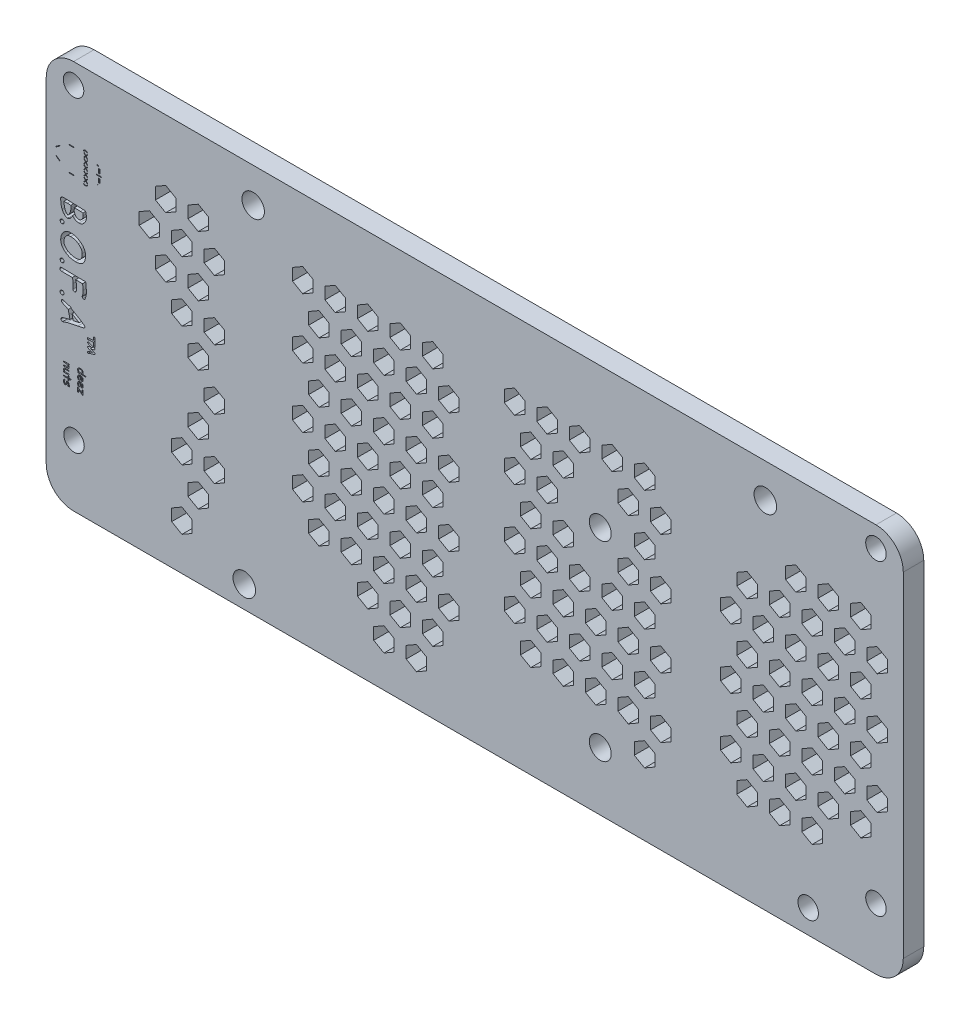
SolidWorks part; units mm, degrees
material "Acrylic (Medium-high impact)"
ref_plane "Front Plane" through (0, 0, 0) normal (0, 0, 1) x (1, 0, 0)
ref_plane "Top Plane" through (0, 0, 0) normal (0, 1, 0) x (1, 0, 0)
ref_plane "Right Plane" through (0, 0, 0) normal (1, 0, 0) x (0, 0, -1)
sketch "Sketch1" plane through (0, 0, 0) normal (0, 0, 1) x (1, 0, 0)
  line L1 (-44.0683, 22.5068) -> (73.4317, 22.5068)
  line L2 (-48.0683, 18.5068) -> (-48.0683, -30.4932)
  line L3 (-44.0683, -34.4932) -> (73.4317, -34.4932)
  line L4 (77.4317, 18.5068) -> (77.4317, -30.4932)
  line L41 (-32.9586, 9.1449) -> (-34.4586, 8.2789)
  line L42 (-34.4586, 8.2789) -> (-34.4586, 6.5468)
  line L43 (-34.4586, 6.5468) -> (-32.9586, 5.6808)
  line L44 (-32.9586, 5.6808) -> (-31.4586, 6.5468)
  line L45 (-31.4586, 6.5468) -> (-31.4586, 8.2789)
  line L46 (-31.4586, 8.2789) -> (-32.9586, 9.1449)
  line L47 (-30.5742, 13.5468) -> (-32.0742, 12.6808)
  line L48 (-32.0742, 12.6808) -> (-32.0742, 10.9488)
  line L49 (-32.0742, 10.9488) -> (-30.5742, 10.0827)
  line L50 (-30.5742, 10.0827) -> (-29.0742, 10.9488)
  line L51 (-29.0742, 10.9488) -> (-29.0742, 12.6808)
  line L52 (-29.0742, 12.6808) -> (-30.5742, 13.5468)
  line L53 (-28.1986, 9.1449) -> (-29.6986, 8.2789)
  line L54 (-29.6986, 8.2789) -> (-29.6986, 6.5468)
  line L55 (-29.6986, 6.5468) -> (-28.1986, 5.6808)
  line L56 (-28.1986, 5.6808) -> (-26.6986, 6.5468)
  line L57 (-26.6986, 6.5468) -> (-26.6986, 8.2789)
  line L58 (-26.6986, 8.2789) -> (-28.1986, 9.1449)
  line L59 (-25.8142, 13.5468) -> (-27.3142, 12.6808)
  line L60 (-27.3142, 12.6808) -> (-27.3142, 10.9488)
  line L61 (-27.3142, 10.9488) -> (-25.8142, 10.0827)
  line L62 (-25.8142, 10.0827) -> (-24.3142, 10.9488)
  line L63 (-24.3142, 10.9488) -> (-24.3142, 12.6808)
  line L64 (-24.3142, 12.6808) -> (-25.8142, 13.5468)
  line L65 (-23.4386, 9.1449) -> (-24.9386, 8.2789)
  line L66 (-24.9386, 8.2789) -> (-24.9386, 6.5468)
  line L67 (-24.9386, 6.5468) -> (-23.4386, 5.6808)
  line L68 (-23.4386, 5.6808) -> (-21.9386, 6.5468)
  line L69 (-21.9386, 6.5468) -> (-21.9386, 8.2789)
  line L70 (-21.9386, 8.2789) -> (-23.4386, 9.1449)
  line L95 (-30.5742, 4.7468) -> (-32.0742, 3.8808)
  line L96 (-32.0742, 3.8808) -> (-32.0742, 2.1488)
  line L97 (-32.0742, 2.1488) -> (-30.5742, 1.2827)
  line L98 (-30.5742, 1.2827) -> (-29.0742, 2.1488)
  line L99 (-29.0742, 2.1488) -> (-29.0742, 3.8808)
  line L100 (-29.0742, 3.8808) -> (-30.5742, 4.7468)
  line L101 (-28.1986, 0.3449) -> (-29.6986, -0.5211)
  line L102 (-29.6986, -0.5211) -> (-29.6986, -2.2532)
  line L103 (-29.6986, -2.2532) -> (-28.1986, -3.1192)
  line L104 (-28.1986, -3.1192) -> (-26.6986, -2.2532)
  line L105 (-26.6986, -2.2532) -> (-26.6986, -0.5211)
  line L106 (-26.6986, -0.5211) -> (-28.1986, 0.3449)
  line L107 (-25.8142, 4.7468) -> (-27.3142, 3.8808)
  line L108 (-27.3142, 3.8808) -> (-27.3142, 2.1488)
  line L109 (-27.3142, 2.1488) -> (-25.8142, 1.2827)
  line L110 (-25.8142, 1.2827) -> (-24.3142, 2.1488)
  line L111 (-24.3142, 2.1488) -> (-24.3142, 3.8808)
  line L112 (-24.3142, 3.8808) -> (-25.8142, 4.7468)
  line L113 (-23.4386, 0.3449) -> (-24.9386, -0.5211)
  line L114 (-24.9386, -0.5211) -> (-24.9386, -2.2532)
  line L115 (-24.9386, -2.2532) -> (-23.4386, -3.1192)
  line L116 (-23.4386, -3.1192) -> (-21.9386, -2.2532)
  line L117 (-21.9386, -2.2532) -> (-21.9386, -0.5211)
  line L118 (-21.9386, -0.5211) -> (-23.4386, 0.3449)
  line L155 (-25.8142, -4.0532) -> (-27.3142, -4.9192)
  line L156 (-27.3142, -4.9192) -> (-27.3142, -6.6512)
  line L157 (-27.3142, -6.6512) -> (-25.8142, -7.5173)
  line L158 (-25.8142, -7.5173) -> (-24.3142, -6.6512)
  line L159 (-24.3142, -6.6512) -> (-24.3142, -4.9192)
  line L160 (-24.3142, -4.9192) -> (-25.8142, -4.0532)
  line L161 (-23.4386, -8.4551) -> (-24.9386, -9.3211)
  line L162 (-24.9386, -9.3211) -> (-24.9386, -11.0532)
  line L163 (-24.9386, -11.0532) -> (-23.4386, -11.9192)
  line L164 (-23.4386, -11.9192) -> (-21.9386, -11.0532)
  line L165 (-21.9386, -11.0532) -> (-21.9386, -9.3211)
  line L166 (-21.9386, -9.3211) -> (-23.4386, -8.4551)
  line L197 (-28.1986, -17.2551) -> (-29.6986, -18.1211)
  line L198 (-29.6986, -18.1211) -> (-29.6986, -19.8532)
  line L199 (-29.6986, -19.8532) -> (-28.1986, -20.7192)
  line L200 (-28.1986, -20.7192) -> (-26.6986, -19.8532)
  line L201 (-26.6986, -19.8532) -> (-26.6986, -18.1211)
  line L202 (-26.6986, -18.1211) -> (-28.1986, -17.2551)
  line L203 (-25.8142, -12.8532) -> (-27.3142, -13.7192)
  line L204 (-27.3142, -13.7192) -> (-27.3142, -15.4512)
  line L205 (-27.3142, -15.4512) -> (-25.8142, -16.3173)
  line L206 (-25.8142, -16.3173) -> (-24.3142, -15.4512)
  line L207 (-24.3142, -15.4512) -> (-24.3142, -13.7192)
  line L208 (-24.3142, -13.7192) -> (-25.8142, -12.8532)
  line L209 (-23.4386, -17.2551) -> (-24.9386, -18.1211)
  line L210 (-24.9386, -18.1211) -> (-24.9386, -19.8532)
  line L211 (-24.9386, -19.8532) -> (-23.4386, -20.7192)
  line L212 (-23.4386, -20.7192) -> (-21.9386, -19.8532)
  line L213 (-21.9386, -19.8532) -> (-21.9386, -18.1211)
  line L214 (-21.9386, -18.1211) -> (-23.4386, -17.2551)
  line L245 (-28.1986, -26.0551) -> (-29.6986, -26.9211)
  line L246 (-29.6986, -26.9211) -> (-29.6986, -28.6532)
  line L247 (-29.6986, -28.6532) -> (-28.1986, -29.5192)
  line L248 (-28.1986, -29.5192) -> (-26.6986, -28.6532)
  line L249 (-26.6986, -28.6532) -> (-26.6986, -26.9211)
  line L250 (-26.6986, -26.9211) -> (-28.1986, -26.0551)
  line L251 (-25.8142, -21.6532) -> (-27.3142, -22.5192)
  line L252 (-27.3142, -22.5192) -> (-27.3142, -24.2512)
  line L253 (-27.3142, -24.2512) -> (-25.8142, -25.1173)
  line L254 (-25.8142, -25.1173) -> (-24.3142, -24.2512)
  line L255 (-24.3142, -24.2512) -> (-24.3142, -22.5192)
  line L256 (-24.3142, -22.5192) -> (-25.8142, -21.6532)
  line L347 (54.5534, 7.152) -> (53.0534, 6.286)
  line L348 (53.0534, 6.286) -> (53.0534, 4.554)
  line L349 (53.0534, 4.554) -> (54.5534, 3.6879)
  line L350 (54.5534, 3.6879) -> (56.0534, 4.554)
  line L351 (56.0534, 4.554) -> (56.0534, 6.286)
  line L352 (56.0534, 6.286) -> (54.5534, 7.152)
  line L359 (59.3134, 7.152) -> (57.8134, 6.286)
  line L360 (57.8134, 6.286) -> (57.8134, 4.554)
  line L361 (57.8134, 4.554) -> (59.3134, 3.6879)
  line L362 (59.3134, 3.6879) -> (60.8134, 4.554)
  line L363 (60.8134, 4.554) -> (60.8134, 6.286)
  line L364 (60.8134, 6.286) -> (59.3134, 7.152)
  line L365 (61.6978, 11.554) -> (60.1978, 10.6879)
  line L366 (60.1978, 10.6879) -> (60.1978, 8.9559)
  line L367 (60.1978, 8.9559) -> (61.6978, 8.0899)
  line L368 (61.6978, 8.0899) -> (63.1978, 8.9559)
  line L369 (63.1978, 8.9559) -> (63.1978, 10.6879)
  line L370 (63.1978, 10.6879) -> (61.6978, 11.554)
  line L371 (64.0734, 7.152) -> (62.5734, 6.286)
  line L372 (62.5734, 6.286) -> (62.5734, 4.554)
  line L373 (62.5734, 4.554) -> (64.0734, 3.6879)
  line L374 (64.0734, 3.6879) -> (65.5734, 4.554)
  line L375 (65.5734, 4.554) -> (65.5734, 6.286)
  line L376 (65.5734, 6.286) -> (64.0734, 7.152)
  line L377 (66.4578, 11.554) -> (64.9578, 10.6879)
  line L378 (64.9578, 10.6879) -> (64.9578, 8.9559)
  line L379 (64.9578, 8.9559) -> (66.4578, 8.0899)
  line L380 (66.4578, 8.0899) -> (67.9578, 8.9559)
  line L381 (67.9578, 8.9559) -> (67.9578, 10.6879)
  line L382 (67.9578, 10.6879) -> (66.4578, 11.554)
  line L383 (68.8334, 7.152) -> (67.3334, 6.286)
  line L384 (67.3334, 6.286) -> (67.3334, 4.554)
  line L385 (67.3334, 4.554) -> (68.8334, 3.6879)
  line L386 (68.8334, 3.6879) -> (70.3334, 4.554)
  line L387 (70.3334, 4.554) -> (70.3334, 6.286)
  line L388 (70.3334, 6.286) -> (68.8334, 7.152)
  line L389 (71.2178, 11.554) -> (69.7178, 10.6879)
  line L390 (69.7178, 10.6879) -> (69.7178, 8.9559)
  line L391 (69.7178, 8.9559) -> (71.2178, 8.0899)
  line L392 (71.2178, 8.0899) -> (72.7178, 8.9559)
  line L393 (72.7178, 8.9559) -> (72.7178, 10.6879)
  line L394 (72.7178, 10.6879) -> (71.2178, 11.554)
  line L395 (73.5934, 7.152) -> (72.0934, 6.286)
  line L396 (72.0934, 6.286) -> (72.0934, 4.554)
  line L397 (72.0934, 4.554) -> (73.5934, 3.6879)
  line L398 (73.5934, 3.6879) -> (75.0934, 4.554)
  line L399 (75.0934, 4.554) -> (75.0934, 6.286)
  line L400 (75.0934, 6.286) -> (73.5934, 7.152)
  line L401 (56.9378, 2.754) -> (55.4378, 1.8879)
  line L402 (55.4378, 1.8879) -> (55.4378, 0.1559)
  line L403 (55.4378, 0.1559) -> (56.9378, -0.7101)
  line L404 (56.9378, -0.7101) -> (58.4378, 0.1559)
  line L405 (58.4378, 0.1559) -> (58.4378, 1.8879)
  line L406 (58.4378, 1.8879) -> (56.9378, 2.754)
  line L407 (59.3134, -1.648) -> (57.8134, -2.514)
  line L408 (57.8134, -2.514) -> (57.8134, -4.246)
  line L409 (57.8134, -4.246) -> (59.3134, -5.1121)
  line L410 (59.3134, -5.1121) -> (60.8134, -4.246)
  line L411 (60.8134, -4.246) -> (60.8134, -2.514)
  line L412 (60.8134, -2.514) -> (59.3134, -1.648)
  line L413 (61.6978, 2.754) -> (60.1978, 1.8879)
  line L414 (60.1978, 1.8879) -> (60.1978, 0.1559)
  line L415 (60.1978, 0.1559) -> (61.6978, -0.7101)
  line L416 (61.6978, -0.7101) -> (63.1978, 0.1559)
  line L417 (63.1978, 0.1559) -> (63.1978, 1.8879)
  line L418 (63.1978, 1.8879) -> (61.6978, 2.754)
  line L419 (64.0734, -1.648) -> (62.5734, -2.514)
  line L420 (62.5734, -2.514) -> (62.5734, -4.246)
  line L421 (62.5734, -4.246) -> (64.0734, -5.1121)
  line L422 (64.0734, -5.1121) -> (65.5734, -4.246)
  line L423 (65.5734, -4.246) -> (65.5734, -2.514)
  line L424 (65.5734, -2.514) -> (64.0734, -1.648)
  line L425 (66.4578, 2.754) -> (64.9578, 1.8879)
  line L426 (64.9578, 1.8879) -> (64.9578, 0.1559)
  line L427 (64.9578, 0.1559) -> (66.4578, -0.7101)
  line L428 (66.4578, -0.7101) -> (67.9578, 0.1559)
  line L429 (67.9578, 0.1559) -> (67.9578, 1.8879)
  line L430 (67.9578, 1.8879) -> (66.4578, 2.754)
  line L431 (68.8334, -1.648) -> (67.3334, -2.514)
  line L432 (67.3334, -2.514) -> (67.3334, -4.246)
  line L433 (67.3334, -4.246) -> (68.8334, -5.1121)
  line L434 (68.8334, -5.1121) -> (70.3334, -4.246)
  line L435 (70.3334, -4.246) -> (70.3334, -2.514)
  line L436 (70.3334, -2.514) -> (68.8334, -1.648)
  line L437 (71.2178, 2.754) -> (69.7178, 1.8879)
  line L438 (69.7178, 1.8879) -> (69.7178, 0.1559)
  line L439 (69.7178, 0.1559) -> (71.2178, -0.7101)
  line L440 (71.2178, -0.7101) -> (72.7178, 0.1559)
  line L441 (72.7178, 0.1559) -> (72.7178, 1.8879)
  line L442 (72.7178, 1.8879) -> (71.2178, 2.754)
  line L443 (73.5934, -1.648) -> (72.0934, -2.514)
  line L444 (72.0934, -2.514) -> (72.0934, -4.246)
  line L445 (72.0934, -4.246) -> (73.5934, -5.1121)
  line L446 (73.5934, -5.1121) -> (75.0934, -4.246)
  line L447 (75.0934, -4.246) -> (75.0934, -2.514)
  line L448 (75.0934, -2.514) -> (73.5934, -1.648)
  line L449 (56.9378, -6.046) -> (55.4378, -6.9121)
  line L450 (55.4378, -6.9121) -> (55.4378, -8.6441)
  line L451 (55.4378, -8.6441) -> (56.9378, -9.5101)
  line L452 (56.9378, -9.5101) -> (58.4378, -8.6441)
  line L453 (58.4378, -8.6441) -> (58.4378, -6.9121)
  line L454 (58.4378, -6.9121) -> (56.9378, -6.046)
  line L455 (59.3134, -10.448) -> (57.8134, -11.314)
  line L456 (57.8134, -11.314) -> (57.8134, -13.046)
  line L457 (57.8134, -13.046) -> (59.3134, -13.9121)
  line L458 (59.3134, -13.9121) -> (60.8134, -13.046)
  line L459 (60.8134, -13.046) -> (60.8134, -11.314)
  line L460 (60.8134, -11.314) -> (59.3134, -10.448)
  line L461 (61.6978, -6.046) -> (60.1978, -6.9121)
  line L462 (60.1978, -6.9121) -> (60.1978, -8.6441)
  line L463 (60.1978, -8.6441) -> (61.6978, -9.5101)
  line L464 (61.6978, -9.5101) -> (63.1978, -8.6441)
  line L465 (63.1978, -8.6441) -> (63.1978, -6.9121)
  line L466 (63.1978, -6.9121) -> (61.6978, -6.046)
  line L467 (64.0734, -10.448) -> (62.5734, -11.314)
  line L468 (62.5734, -11.314) -> (62.5734, -13.046)
  line L469 (62.5734, -13.046) -> (64.0734, -13.9121)
  line L470 (64.0734, -13.9121) -> (65.5734, -13.046)
  line L471 (65.5734, -13.046) -> (65.5734, -11.314)
  line L472 (65.5734, -11.314) -> (64.0734, -10.448)
  line L473 (66.4578, -6.046) -> (64.9578, -6.9121)
  line L474 (64.9578, -6.9121) -> (64.9578, -8.6441)
  line L475 (64.9578, -8.6441) -> (66.4578, -9.5101)
  line L476 (66.4578, -9.5101) -> (67.9578, -8.6441)
  line L477 (67.9578, -8.6441) -> (67.9578, -6.9121)
  line L478 (67.9578, -6.9121) -> (66.4578, -6.046)
  line L479 (68.8334, -10.448) -> (67.3334, -11.314)
  line L480 (67.3334, -11.314) -> (67.3334, -13.046)
  line L481 (67.3334, -13.046) -> (68.8334, -13.9121)
  line L482 (68.8334, -13.9121) -> (70.3334, -13.046)
  line L483 (70.3334, -13.046) -> (70.3334, -11.314)
  line L484 (70.3334, -11.314) -> (68.8334, -10.448)
  line L485 (71.2178, -6.046) -> (69.7178, -6.9121)
  line L486 (69.7178, -6.9121) -> (69.7178, -8.6441)
  line L487 (69.7178, -8.6441) -> (71.2178, -9.5101)
  line L488 (71.2178, -9.5101) -> (72.7178, -8.6441)
  line L489 (72.7178, -8.6441) -> (72.7178, -6.9121)
  line L490 (72.7178, -6.9121) -> (71.2178, -6.046)
  line L491 (73.5934, -10.448) -> (72.0934, -11.314)
  line L492 (72.0934, -11.314) -> (72.0934, -13.046)
  line L493 (72.0934, -13.046) -> (73.5934, -13.9121)
  line L494 (73.5934, -13.9121) -> (75.0934, -13.046)
  line L495 (75.0934, -13.046) -> (75.0934, -11.314)
  line L496 (75.0934, -11.314) -> (73.5934, -10.448)
  line L497 (56.9378, -14.846) -> (55.4378, -15.7121)
  line L498 (55.4378, -15.7121) -> (55.4378, -17.4441)
  line L499 (55.4378, -17.4441) -> (56.9378, -18.3101)
  line L500 (56.9378, -18.3101) -> (58.4378, -17.4441)
  line L501 (58.4378, -17.4441) -> (58.4378, -15.7121)
  line L502 (58.4378, -15.7121) -> (56.9378, -14.846)
  line L503 (59.3134, -19.248) -> (57.8134, -20.114)
  line L504 (57.8134, -20.114) -> (57.8134, -21.846)
  line L505 (57.8134, -21.846) -> (59.3134, -22.7121)
  line L506 (59.3134, -22.7121) -> (60.8134, -21.846)
  line L507 (60.8134, -21.846) -> (60.8134, -20.114)
  line L508 (60.8134, -20.114) -> (59.3134, -19.248)
  line L509 (61.6978, -14.846) -> (60.1978, -15.7121)
  line L510 (60.1978, -15.7121) -> (60.1978, -17.4441)
  line L511 (60.1978, -17.4441) -> (61.6978, -18.3101)
  line L512 (61.6978, -18.3101) -> (63.1978, -17.4441)
  line L513 (63.1978, -17.4441) -> (63.1978, -15.7121)
  line L514 (63.1978, -15.7121) -> (61.6978, -14.846)
  line L515 (64.0734, -19.248) -> (62.5734, -20.114)
  line L516 (62.5734, -20.114) -> (62.5734, -21.846)
  line L517 (62.5734, -21.846) -> (64.0734, -22.7121)
  line L518 (64.0734, -22.7121) -> (65.5734, -21.846)
  line L519 (65.5734, -21.846) -> (65.5734, -20.114)
  line L520 (65.5734, -20.114) -> (64.0734, -19.248)
  line L521 (66.4578, -14.846) -> (64.9578, -15.7121)
  line L522 (64.9578, -15.7121) -> (64.9578, -17.4441)
  line L523 (64.9578, -17.4441) -> (66.4578, -18.3101)
  line L524 (66.4578, -18.3101) -> (67.9578, -17.4441)
  line L525 (67.9578, -17.4441) -> (67.9578, -15.7121)
  line L526 (67.9578, -15.7121) -> (66.4578, -14.846)
  line L533 (71.2178, -14.846) -> (69.7178, -15.7121)
  line L534 (69.7178, -15.7121) -> (69.7178, -17.4441)
  line L535 (69.7178, -17.4441) -> (71.2178, -18.3101)
  line L536 (71.2178, -18.3101) -> (72.7178, -17.4441)
  line L537 (72.7178, -17.4441) -> (72.7178, -15.7121)
  line L538 (72.7178, -15.7121) -> (71.2178, -14.846)
  line L575 (52.1778, 2.754) -> (50.6778, 1.8879)
  line L576 (50.6778, 1.8879) -> (50.6778, 0.1559)
  line L577 (50.6778, 0.1559) -> (52.1778, -0.7101)
  line L578 (52.1778, -0.7101) -> (53.6778, 0.1559)
  line L579 (53.6778, 0.1559) -> (53.6778, 1.8879)
  line L580 (53.6778, 1.8879) -> (52.1778, 2.754)
  line L581 (54.5534, -1.648) -> (53.0534, -2.514)
  line L582 (53.0534, -2.514) -> (53.0534, -4.246)
  line L583 (53.0534, -4.246) -> (54.5534, -5.1121)
  line L584 (54.5534, -5.1121) -> (56.0534, -4.246)
  line L585 (56.0534, -4.246) -> (56.0534, -2.514)
  line L586 (56.0534, -2.514) -> (54.5534, -1.648)
  line L587 (52.1778, -6.046) -> (50.6778, -6.9121)
  line L588 (50.6778, -6.9121) -> (50.6778, -8.6441)
  line L589 (50.6778, -8.6441) -> (52.1778, -9.5101)
  line L590 (52.1778, -9.5101) -> (53.6778, -8.6441)
  line L591 (53.6778, -8.6441) -> (53.6778, -6.9121)
  line L592 (53.6778, -6.9121) -> (52.1778, -6.046)
  line L593 (54.5534, -10.448) -> (53.0534, -11.314)
  line L594 (53.0534, -11.314) -> (53.0534, -13.046)
  line L595 (53.0534, -13.046) -> (54.5534, -13.9121)
  line L596 (54.5534, -13.9121) -> (56.0534, -13.046)
  line L597 (56.0534, -13.046) -> (56.0534, -11.314)
  line L598 (56.0534, -11.314) -> (54.5534, -10.448)
  line L599 (52.1778, -14.846) -> (50.6778, -15.7121)
  line L600 (50.6778, -15.7121) -> (50.6778, -17.4441)
  line L601 (50.6778, -17.4441) -> (52.1778, -18.3101)
  line L602 (52.1778, -18.3101) -> (53.6778, -17.4441)
  line L603 (53.6778, -17.4441) -> (53.6778, -15.7121)
  line L604 (53.6778, -15.7121) -> (52.1778, -14.846)
  line L605 (54.5534, -19.248) -> (53.0534, -20.114)
  line L606 (53.0534, -20.114) -> (53.0534, -21.846)
  line L607 (53.0534, -21.846) -> (54.5534, -22.7121)
  line L608 (54.5534, -22.7121) -> (56.0534, -21.846)
  line L609 (56.0534, -21.846) -> (56.0534, -20.114)
  line L610 (56.0534, -20.114) -> (54.5534, -19.248)
  line L611 (-10.5093, 13.2923) -> (-12.0093, 12.4263)
  line L612 (-12.0093, 12.4263) -> (-12.0093, 10.6942)
  line L613 (-12.0093, 10.6942) -> (-10.5093, 9.8282)
  line L614 (-10.5093, 9.8282) -> (-9.0093, 10.6942)
  line L615 (-9.0093, 10.6942) -> (-9.0093, 12.4263)
  line L616 (-9.0093, 12.4263) -> (-10.5093, 13.2923)
  line L617 (-8.1336, 8.8904) -> (-9.6336, 8.0244)
  line L618 (-9.6336, 8.0244) -> (-9.6336, 6.2923)
  line L619 (-9.6336, 6.2923) -> (-8.1336, 5.4263)
  line L620 (-8.1336, 5.4263) -> (-6.6336, 6.2923)
  line L621 (-6.6336, 6.2923) -> (-6.6336, 8.0244)
  line L622 (-6.6336, 8.0244) -> (-8.1336, 8.8904)
  line L623 (-5.7493, 13.2923) -> (-7.2493, 12.4263)
  line L624 (-7.2493, 12.4263) -> (-7.2493, 10.6942)
  line L625 (-7.2493, 10.6942) -> (-5.7493, 9.8282)
  line L626 (-5.7493, 9.8282) -> (-4.2493, 10.6942)
  line L627 (-4.2493, 10.6942) -> (-4.2493, 12.4263)
  line L628 (-4.2493, 12.4263) -> (-5.7493, 13.2923)
  line L629 (-3.3736, 8.8904) -> (-4.8736, 8.0244)
  line L630 (-4.8736, 8.0244) -> (-4.8736, 6.2923)
  line L631 (-4.8736, 6.2923) -> (-3.3736, 5.4263)
  line L632 (-3.3736, 5.4263) -> (-1.8736, 6.2923)
  line L633 (-1.8736, 6.2923) -> (-1.8736, 8.0244)
  line L634 (-1.8736, 8.0244) -> (-3.3736, 8.8904)
  line L635 (-0.9893, 13.2923) -> (-2.4893, 12.4263)
  line L636 (-2.4893, 12.4263) -> (-2.4893, 10.6942)
  line L637 (-2.4893, 10.6942) -> (-0.9893, 9.8282)
  line L638 (-0.9893, 9.8282) -> (0.5107, 10.6942)
  line L639 (0.5107, 10.6942) -> (0.5107, 12.4263)
  line L640 (0.5107, 12.4263) -> (-0.9893, 13.2923)
  line L641 (1.3864, 8.8904) -> (-0.1136, 8.0244)
  line L642 (-0.1136, 8.0244) -> (-0.1136, 6.2923)
  line L643 (-0.1136, 6.2923) -> (1.3864, 5.4263)
  line L644 (1.3864, 5.4263) -> (2.8864, 6.2923)
  line L645 (2.8864, 6.2923) -> (2.8864, 8.0244)
  line L646 (2.8864, 8.0244) -> (1.3864, 8.8904)
  line L647 (3.7707, 13.2923) -> (2.2707, 12.4263)
  line L648 (2.2707, 12.4263) -> (2.2707, 10.6942)
  line L649 (2.2707, 10.6942) -> (3.7707, 9.8282)
  line L650 (3.7707, 9.8282) -> (5.2707, 10.6942)
  line L651 (5.2707, 10.6942) -> (5.2707, 12.4263)
  line L652 (5.2707, 12.4263) -> (3.7707, 13.2923)
  line L653 (6.1464, 8.8904) -> (4.6464, 8.0244)
  line L654 (4.6464, 8.0244) -> (4.6464, 6.2923)
  line L655 (4.6464, 6.2923) -> (6.1464, 5.4263)
  line L656 (6.1464, 5.4263) -> (7.6464, 6.2923)
  line L657 (7.6464, 6.2923) -> (7.6464, 8.0244)
  line L658 (7.6464, 8.0244) -> (6.1464, 8.8904)
  line L659 (8.5307, 13.2923) -> (7.0307, 12.4263)
  line L660 (7.0307, 12.4263) -> (7.0307, 10.6942)
  line L661 (7.0307, 10.6942) -> (8.5307, 9.8282)
  line L662 (8.5307, 9.8282) -> (10.0307, 10.6942)
  line L663 (10.0307, 10.6942) -> (10.0307, 12.4263)
  line L664 (10.0307, 12.4263) -> (8.5307, 13.2923)
  line L665 (10.9064, 8.8904) -> (9.4064, 8.0244)
  line L666 (9.4064, 8.0244) -> (9.4064, 6.2923)
  line L667 (9.4064, 6.2923) -> (10.9064, 5.4263)
  line L668 (10.9064, 5.4263) -> (12.4064, 6.2923)
  line L669 (12.4064, 6.2923) -> (12.4064, 8.0244)
  line L670 (12.4064, 8.0244) -> (10.9064, 8.8904)
  line L671 (-5.7493, 4.4923) -> (-7.2493, 3.6263)
  line L672 (-7.2493, 3.6263) -> (-7.2493, 1.8942)
  line L673 (-7.2493, 1.8942) -> (-5.7493, 1.0282)
  line L674 (-5.7493, 1.0282) -> (-4.2493, 1.8942)
  line L675 (-4.2493, 1.8942) -> (-4.2493, 3.6263)
  line L676 (-4.2493, 3.6263) -> (-5.7493, 4.4923)
  line L677 (-3.3736, 0.0904) -> (-4.8736, -0.7756)
  line L678 (-4.8736, -0.7756) -> (-4.8736, -2.5077)
  line L679 (-4.8736, -2.5077) -> (-3.3736, -3.3737)
  line L680 (-3.3736, -3.3737) -> (-1.8736, -2.5077)
  line L681 (-1.8736, -2.5077) -> (-1.8736, -0.7756)
  line L682 (-1.8736, -0.7756) -> (-3.3736, 0.0904)
  line L683 (-0.9893, 4.4923) -> (-2.4893, 3.6263)
  line L684 (-2.4893, 3.6263) -> (-2.4893, 1.8942)
  line L685 (-2.4893, 1.8942) -> (-0.9893, 1.0282)
  line L686 (-0.9893, 1.0282) -> (0.5107, 1.8942)
  line L687 (0.5107, 1.8942) -> (0.5107, 3.6263)
  line L688 (0.5107, 3.6263) -> (-0.9893, 4.4923)
  line L689 (1.3864, 0.0904) -> (-0.1136, -0.7756)
  line L690 (-0.1136, -0.7756) -> (-0.1136, -2.5077)
  line L691 (-0.1136, -2.5077) -> (1.3864, -3.3737)
  line L692 (1.3864, -3.3737) -> (2.8864, -2.5077)
  line L693 (2.8864, -2.5077) -> (2.8864, -0.7756)
  line L694 (2.8864, -0.7756) -> (1.3864, 0.0904)
  line L695 (3.7707, 4.4923) -> (2.2707, 3.6263)
  line L696 (2.2707, 3.6263) -> (2.2707, 1.8942)
  line L697 (2.2707, 1.8942) -> (3.7707, 1.0282)
  line L698 (3.7707, 1.0282) -> (5.2707, 1.8942)
  line L699 (5.2707, 1.8942) -> (5.2707, 3.6263)
  line L700 (5.2707, 3.6263) -> (3.7707, 4.4923)
  line L701 (6.1464, 0.0904) -> (4.6464, -0.7756)
  line L702 (4.6464, -0.7756) -> (4.6464, -2.5077)
  line L703 (4.6464, -2.5077) -> (6.1464, -3.3737)
  line L704 (6.1464, -3.3737) -> (7.6464, -2.5077)
  line L705 (7.6464, -2.5077) -> (7.6464, -0.7756)
  line L706 (7.6464, -0.7756) -> (6.1464, 0.0904)
  line L707 (8.5307, 4.4923) -> (7.0307, 3.6263)
  line L708 (7.0307, 3.6263) -> (7.0307, 1.8942)
  line L709 (7.0307, 1.8942) -> (8.5307, 1.0282)
  line L710 (8.5307, 1.0282) -> (10.0307, 1.8942)
  line L711 (10.0307, 1.8942) -> (10.0307, 3.6263)
  line L712 (10.0307, 3.6263) -> (8.5307, 4.4923)
  line L713 (10.9064, 0.0904) -> (9.4064, -0.7756)
  line L714 (9.4064, -0.7756) -> (9.4064, -2.5077)
  line L715 (9.4064, -2.5077) -> (10.9064, -3.3737)
  line L716 (10.9064, -3.3737) -> (12.4064, -2.5077)
  line L717 (12.4064, -2.5077) -> (12.4064, -0.7756)
  line L718 (12.4064, -0.7756) -> (10.9064, 0.0904)
  line L719 (-5.7493, -4.3077) -> (-7.2493, -5.1737)
  line L720 (-7.2493, -5.1737) -> (-7.2493, -6.9058)
  line L721 (-7.2493, -6.9058) -> (-5.7493, -7.7718)
  line L722 (-5.7493, -7.7718) -> (-4.2493, -6.9058)
  line L723 (-4.2493, -6.9058) -> (-4.2493, -5.1737)
  line L724 (-4.2493, -5.1737) -> (-5.7493, -4.3077)
  line L725 (-3.3736, -8.7096) -> (-4.8736, -9.5756)
  line L726 (-4.8736, -9.5756) -> (-4.8736, -11.3077)
  line L727 (-4.8736, -11.3077) -> (-3.3736, -12.1737)
  line L728 (-3.3736, -12.1737) -> (-1.8736, -11.3077)
  line L729 (-1.8736, -11.3077) -> (-1.8736, -9.5756)
  line L730 (-1.8736, -9.5756) -> (-3.3736, -8.7096)
  line L731 (-0.9893, -4.3077) -> (-2.4893, -5.1737)
  line L732 (-2.4893, -5.1737) -> (-2.4893, -6.9058)
  line L733 (-2.4893, -6.9058) -> (-0.9893, -7.7718)
  line L734 (-0.9893, -7.7718) -> (0.5107, -6.9058)
  line L735 (0.5107, -6.9058) -> (0.5107, -5.1737)
  line L736 (0.5107, -5.1737) -> (-0.9893, -4.3077)
  line L737 (1.3864, -8.7096) -> (-0.1136, -9.5756)
  line L738 (-0.1136, -9.5756) -> (-0.1136, -11.3077)
  line L739 (-0.1136, -11.3077) -> (1.3864, -12.1737)
  line L740 (1.3864, -12.1737) -> (2.8864, -11.3077)
  line L741 (2.8864, -11.3077) -> (2.8864, -9.5756)
  line L742 (2.8864, -9.5756) -> (1.3864, -8.7096)
  line L743 (3.7707, -4.3077) -> (2.2707, -5.1737)
  line L744 (2.2707, -5.1737) -> (2.2707, -6.9058)
  line L745 (2.2707, -6.9058) -> (3.7707, -7.7718)
  line L746 (3.7707, -7.7718) -> (5.2707, -6.9058)
  line L747 (5.2707, -6.9058) -> (5.2707, -5.1737)
  line L748 (5.2707, -5.1737) -> (3.7707, -4.3077)
  line L749 (6.1464, -8.7096) -> (4.6464, -9.5756)
  line L750 (4.6464, -9.5756) -> (4.6464, -11.3077)
  line L751 (4.6464, -11.3077) -> (6.1464, -12.1737)
  line L752 (6.1464, -12.1737) -> (7.6464, -11.3077)
  line L753 (7.6464, -11.3077) -> (7.6464, -9.5756)
  line L754 (7.6464, -9.5756) -> (6.1464, -8.7096)
  line L755 (8.5307, -4.3077) -> (7.0307, -5.1737)
  line L756 (7.0307, -5.1737) -> (7.0307, -6.9058)
  line L757 (7.0307, -6.9058) -> (8.5307, -7.7718)
  line L758 (8.5307, -7.7718) -> (10.0307, -6.9058)
  line L759 (10.0307, -6.9058) -> (10.0307, -5.1737)
  line L760 (10.0307, -5.1737) -> (8.5307, -4.3077)
  line L761 (10.9064, -8.7096) -> (9.4064, -9.5756)
  line L762 (9.4064, -9.5756) -> (9.4064, -11.3077)
  line L763 (9.4064, -11.3077) -> (10.9064, -12.1737)
  line L764 (10.9064, -12.1737) -> (12.4064, -11.3077)
  line L765 (12.4064, -11.3077) -> (12.4064, -9.5756)
  line L766 (12.4064, -9.5756) -> (10.9064, -8.7096)
  line L767 (-5.7493, -13.1077) -> (-7.2493, -13.9737)
  line L768 (-7.2493, -13.9737) -> (-7.2493, -15.7058)
  line L769 (-7.2493, -15.7058) -> (-5.7493, -16.5718)
  line L770 (-5.7493, -16.5718) -> (-4.2493, -15.7058)
  line L771 (-4.2493, -15.7058) -> (-4.2493, -13.9737)
  line L772 (-4.2493, -13.9737) -> (-5.7493, -13.1077)
  line L773 (-3.3736, -17.5096) -> (-4.8736, -18.3756)
  line L774 (-4.8736, -18.3756) -> (-4.8736, -20.1077)
  line L775 (-4.8736, -20.1077) -> (-3.3736, -20.9737)
  line L776 (-3.3736, -20.9737) -> (-1.8736, -20.1077)
  line L777 (-1.8736, -20.1077) -> (-1.8736, -18.3756)
  line L778 (-1.8736, -18.3756) -> (-3.3736, -17.5096)
  line L779 (-0.9893, -13.1077) -> (-2.4893, -13.9737)
  line L780 (-2.4893, -13.9737) -> (-2.4893, -15.7058)
  line L781 (-2.4893, -15.7058) -> (-0.9893, -16.5718)
  line L782 (-0.9893, -16.5718) -> (0.5107, -15.7058)
  line L783 (0.5107, -15.7058) -> (0.5107, -13.9737)
  line L784 (0.5107, -13.9737) -> (-0.9893, -13.1077)
  line L785 (1.3864, -17.5096) -> (-0.1136, -18.3756)
  line L786 (-0.1136, -18.3756) -> (-0.1136, -20.1077)
  line L787 (-0.1136, -20.1077) -> (1.3864, -20.9737)
  line L788 (1.3864, -20.9737) -> (2.8864, -20.1077)
  line L789 (2.8864, -20.1077) -> (2.8864, -18.3756)
  line L790 (2.8864, -18.3756) -> (1.3864, -17.5096)
  line L791 (3.7707, -13.1077) -> (2.2707, -13.9737)
  line L792 (2.2707, -13.9737) -> (2.2707, -15.7058)
  line L793 (2.2707, -15.7058) -> (3.7707, -16.5718)
  line L794 (3.7707, -16.5718) -> (5.2707, -15.7058)
  line L795 (5.2707, -15.7058) -> (5.2707, -13.9737)
  line L796 (5.2707, -13.9737) -> (3.7707, -13.1077)
  line L797 (6.1464, -17.5096) -> (4.6464, -18.3756)
  line L798 (4.6464, -18.3756) -> (4.6464, -20.1077)
  line L799 (4.6464, -20.1077) -> (6.1464, -20.9737)
  line L800 (6.1464, -20.9737) -> (7.6464, -20.1077)
  line L801 (7.6464, -20.1077) -> (7.6464, -18.3756)
  line L802 (7.6464, -18.3756) -> (6.1464, -17.5096)
  line L803 (8.5307, -13.1077) -> (7.0307, -13.9737)
  line L804 (7.0307, -13.9737) -> (7.0307, -15.7058)
  line L805 (7.0307, -15.7058) -> (8.5307, -16.5718)
  line L806 (8.5307, -16.5718) -> (10.0307, -15.7058)
  line L807 (10.0307, -15.7058) -> (10.0307, -13.9737)
  line L808 (10.0307, -13.9737) -> (8.5307, -13.1077)
  line L809 (10.9064, -17.5096) -> (9.4064, -18.3756)
  line L810 (9.4064, -18.3756) -> (9.4064, -20.1077)
  line L811 (9.4064, -20.1077) -> (10.9064, -20.9737)
  line L812 (10.9064, -20.9737) -> (12.4064, -20.1077)
  line L813 (12.4064, -20.1077) -> (12.4064, -18.3756)
  line L814 (12.4064, -18.3756) -> (10.9064, -17.5096)
  line L815 (-0.9893, -21.9077) -> (-2.4893, -22.7737)
  line L816 (-2.4893, -22.7737) -> (-2.4893, -24.5058)
  line L817 (-2.4893, -24.5058) -> (-0.9893, -25.3718)
  line L818 (-0.9893, -25.3718) -> (0.5107, -24.5058)
  line L819 (0.5107, -24.5058) -> (0.5107, -22.7737)
  line L820 (0.5107, -22.7737) -> (-0.9893, -21.9077)
  line L821 (1.3864, -26.3096) -> (-0.1136, -27.1756)
  line L822 (-0.1136, -27.1756) -> (-0.1136, -28.9077)
  line L823 (-0.1136, -28.9077) -> (1.3864, -29.7737)
  line L824 (1.3864, -29.7737) -> (2.8864, -28.9077)
  line L825 (2.8864, -28.9077) -> (2.8864, -27.1756)
  line L826 (2.8864, -27.1756) -> (1.3864, -26.3096)
  line L827 (3.7707, -21.9077) -> (2.2707, -22.7737)
  line L828 (2.2707, -22.7737) -> (2.2707, -24.5058)
  line L829 (2.2707, -24.5058) -> (3.7707, -25.3718)
  line L830 (3.7707, -25.3718) -> (5.2707, -24.5058)
  line L831 (5.2707, -24.5058) -> (5.2707, -22.7737)
  line L832 (5.2707, -22.7737) -> (3.7707, -21.9077)
  line L833 (6.1464, -26.3096) -> (4.6464, -27.1756)
  line L834 (4.6464, -27.1756) -> (4.6464, -28.9077)
  line L835 (4.6464, -28.9077) -> (6.1464, -29.7737)
  line L836 (6.1464, -29.7737) -> (7.6464, -28.9077)
  line L837 (7.6464, -28.9077) -> (7.6464, -27.1756)
  line L838 (7.6464, -27.1756) -> (6.1464, -26.3096)
  line L839 (8.5307, -21.9077) -> (7.0307, -22.7737)
  line L840 (7.0307, -22.7737) -> (7.0307, -24.5058)
  line L841 (7.0307, -24.5058) -> (8.5307, -25.3718)
  line L842 (8.5307, -25.3718) -> (10.0307, -24.5058)
  line L843 (10.0307, -24.5058) -> (10.0307, -22.7737)
  line L844 (10.0307, -22.7737) -> (8.5307, -21.9077)
  line L845 (-10.5093, 4.4923) -> (-12.0093, 3.6263)
  line L846 (-12.0093, 3.6263) -> (-12.0093, 1.8942)
  line L847 (-12.0093, 1.8942) -> (-10.5093, 1.0282)
  line L848 (-10.5093, 1.0282) -> (-9.0093, 1.8942)
  line L849 (-9.0093, 1.8942) -> (-9.0093, 3.6263)
  line L850 (-9.0093, 3.6263) -> (-10.5093, 4.4923)
  line L851 (-8.1336, 0.0904) -> (-9.6336, -0.7756)
  line L852 (-9.6336, -0.7756) -> (-9.6336, -2.5077)
  line L853 (-9.6336, -2.5077) -> (-8.1336, -3.3737)
  line L854 (-8.1336, -3.3737) -> (-6.6336, -2.5077)
  line L855 (-6.6336, -2.5077) -> (-6.6336, -0.7756)
  line L856 (-6.6336, -0.7756) -> (-8.1336, 0.0904)
  line L857 (-10.5093, -4.3077) -> (-12.0093, -5.1737)
  line L858 (-12.0093, -5.1737) -> (-12.0093, -6.9058)
  line L859 (-12.0093, -6.9058) -> (-10.5093, -7.7718)
  line L860 (-10.5093, -7.7718) -> (-9.0093, -6.9058)
  line L861 (-9.0093, -6.9058) -> (-9.0093, -5.1737)
  line L862 (-9.0093, -5.1737) -> (-10.5093, -4.3077)
  line L863 (-8.1336, -8.7096) -> (-9.6336, -9.5756)
  line L864 (-9.6336, -9.5756) -> (-9.6336, -11.3077)
  line L865 (-9.6336, -11.3077) -> (-8.1336, -12.1737)
  line L866 (-8.1336, -12.1737) -> (-6.6336, -11.3077)
  line L867 (-6.6336, -11.3077) -> (-6.6336, -9.5756)
  line L868 (-6.6336, -9.5756) -> (-8.1336, -8.7096)
  line L869 (-10.5093, -13.1077) -> (-12.0093, -13.9737)
  line L870 (-12.0093, -13.9737) -> (-12.0093, -15.7058)
  line L871 (-12.0093, -15.7058) -> (-10.5093, -16.5718)
  line L872 (-10.5093, -16.5718) -> (-9.0093, -15.7058)
  line L873 (-9.0093, -15.7058) -> (-9.0093, -13.9737)
  line L874 (-9.0093, -13.9737) -> (-10.5093, -13.1077)
  line L875 (-8.1336, -17.5096) -> (-9.6336, -18.3756)
  line L876 (-9.6336, -18.3756) -> (-9.6336, -20.1077)
  line L877 (-9.6336, -20.1077) -> (-8.1336, -20.9737)
  line L878 (-8.1336, -20.9737) -> (-6.6336, -20.1077)
  line L879 (-6.6336, -20.1077) -> (-6.6336, -18.3756)
  line L880 (-6.6336, -18.3756) -> (-8.1336, -17.5096)
  line L881 (20.5044, 13.3912) -> (19.0044, 12.5251)
  line L882 (19.0044, 12.5251) -> (19.0044, 10.7931)
  line L883 (19.0044, 10.7931) -> (20.5044, 9.9271)
  line L884 (20.5044, 9.9271) -> (22.0044, 10.7931)
  line L885 (22.0044, 10.7931) -> (22.0044, 12.5251)
  line L886 (22.0044, 12.5251) -> (20.5044, 13.3912)
  line L887 (22.8801, 8.9892) -> (21.3801, 8.1232)
  line L888 (21.3801, 8.1232) -> (21.3801, 6.3912)
  line L889 (21.3801, 6.3912) -> (22.8801, 5.5251)
  line L890 (22.8801, 5.5251) -> (24.3801, 6.3912)
  line L891 (24.3801, 6.3912) -> (24.3801, 8.1232)
  line L892 (24.3801, 8.1232) -> (22.8801, 8.9892)
  line L893 (25.2644, 13.3912) -> (23.7644, 12.5251)
  line L894 (23.7644, 12.5251) -> (23.7644, 10.7931)
  line L895 (23.7644, 10.7931) -> (25.2644, 9.9271)
  line L896 (25.2644, 9.9271) -> (26.7644, 10.7931)
  line L897 (26.7644, 10.7931) -> (26.7644, 12.5251)
  line L898 (26.7644, 12.5251) -> (25.2644, 13.3912)
  line L899 (27.6401, 8.9892) -> (26.1401, 8.1232)
  line L900 (26.1401, 8.1232) -> (26.1401, 6.3912)
  line L901 (26.1401, 6.3912) -> (27.6401, 5.5251)
  line L902 (27.6401, 5.5251) -> (29.1401, 6.3912)
  line L903 (29.1401, 6.3912) -> (29.1401, 8.1232)
  line L904 (29.1401, 8.1232) -> (27.6401, 8.9892)
  line L905 (30.0244, 13.3912) -> (28.5244, 12.5251)
  line L906 (28.5244, 12.5251) -> (28.5244, 10.7931)
  line L907 (28.5244, 10.7931) -> (30.0244, 9.9271)
  line L908 (30.0244, 9.9271) -> (31.5244, 10.7931)
  line L909 (31.5244, 10.7931) -> (31.5244, 12.5251)
  line L910 (31.5244, 12.5251) -> (30.0244, 13.3912)
  line L916 (33.9001, 8.1232) -> (32.4001, 8.9892)
  line L917 (34.7844, 13.3912) -> (33.2844, 12.5251)
  line L918 (33.2844, 12.5251) -> (33.2844, 10.7931)
  line L919 (33.2844, 10.7931) -> (34.7844, 9.9271)
  line L920 (34.7844, 9.9271) -> (36.2844, 10.7931)
  line L921 (36.2844, 10.7931) -> (36.2844, 12.5251)
  line L922 (36.2844, 12.5251) -> (34.7844, 13.3912)
  line L923 (37.1601, 8.9892) -> (35.6601, 8.1232)
  line L924 (35.6601, 8.1232) -> (35.6601, 6.3912)
  line L925 (35.6601, 6.3912) -> (37.1601, 5.5251)
  line L926 (37.1601, 5.5251) -> (38.6601, 6.3912)
  line L927 (38.6601, 6.3912) -> (38.6601, 8.1232)
  line L928 (38.6601, 8.1232) -> (37.1601, 8.9892)
  line L929 (39.5444, 13.3912) -> (38.0444, 12.5251)
  line L930 (38.0444, 12.5251) -> (38.0444, 10.7931)
  line L931 (38.0444, 10.7931) -> (39.5444, 9.9271)
  line L932 (39.5444, 9.9271) -> (41.0444, 10.7931)
  line L933 (41.0444, 10.7931) -> (41.0444, 12.5251)
  line L934 (41.0444, 12.5251) -> (39.5444, 13.3912)
  line L935 (41.9201, 8.9892) -> (40.4201, 8.1232)
  line L936 (40.4201, 8.1232) -> (40.4201, 6.3912)
  line L937 (40.4201, 6.3912) -> (41.9201, 5.5251)
  line L938 (41.9201, 5.5251) -> (43.4201, 6.3912)
  line L939 (43.4201, 6.3912) -> (43.4201, 8.1232)
  line L940 (43.4201, 8.1232) -> (41.9201, 8.9892)
  line L941 (25.2644, 4.5912) -> (23.7644, 3.7251)
  line L942 (23.7644, 3.7251) -> (23.7644, 1.9931)
  line L943 (23.7644, 1.9931) -> (25.2644, 1.1271)
  line L944 (25.2644, 1.1271) -> (26.7644, 1.9931)
  line L945 (26.7644, 1.9931) -> (26.7644, 3.7251)
  line L946 (26.7644, 3.7251) -> (25.2644, 4.5912)
  line L947 (27.6401, 0.1892) -> (26.1401, -0.6768)
  line L948 (26.1401, -0.6768) -> (26.1401, -2.4088)
  line L949 (26.1401, -2.4088) -> (27.6401, -3.2749)
  line L950 (27.6401, -3.2749) -> (29.1401, -2.4088)
  line L951 (29.1401, -2.4088) -> (29.1401, -0.6768)
  line L952 (29.1401, -0.6768) -> (27.6401, 0.1892)
  line L971 (37.1601, 0.1892) -> (35.6601, -0.6768)
  line L972 (35.6601, -0.6768) -> (35.6601, -2.4088)
  line L973 (35.6601, -2.4088) -> (37.1601, -3.2749)
  line L974 (37.1601, -3.2749) -> (38.6601, -2.4088)
  line L975 (38.6601, -2.4088) -> (38.6601, -0.6768)
  line L976 (38.6601, -0.6768) -> (37.1601, 0.1892)
  line L977 (39.5444, 4.5912) -> (38.0444, 3.7251)
  line L978 (38.0444, 3.7251) -> (38.0444, 1.9931)
  line L979 (38.0444, 1.9931) -> (39.5444, 1.1271)
  line L980 (39.5444, 1.1271) -> (41.0444, 1.9931)
  line L981 (41.0444, 1.9931) -> (41.0444, 3.7251)
  line L982 (41.0444, 3.7251) -> (39.5444, 4.5912)
  line L983 (41.9201, 0.1892) -> (40.4201, -0.6768)
  line L984 (40.4201, -0.6768) -> (40.4201, -2.4088)
  line L985 (40.4201, -2.4088) -> (41.9201, -3.2749)
  line L986 (41.9201, -3.2749) -> (43.4201, -2.4088)
  line L987 (43.4201, -2.4088) -> (43.4201, -0.6768)
  line L988 (43.4201, -0.6768) -> (41.9201, 0.1892)
  line L989 (25.2644, -4.2088) -> (23.7644, -5.0749)
  line L990 (23.7644, -5.0749) -> (23.7644, -6.8069)
  line L991 (23.7644, -6.8069) -> (25.2644, -7.6729)
  line L992 (25.2644, -7.6729) -> (26.7644, -6.8069)
  line L993 (26.7644, -6.8069) -> (26.7644, -5.0749)
  line L994 (26.7644, -5.0749) -> (25.2644, -4.2088)
  line L995 (27.6401, -8.6108) -> (26.1401, -9.4768)
  line L996 (26.1401, -9.4768) -> (26.1401, -11.2088)
  line L997 (26.1401, -11.2088) -> (27.6401, -12.0749)
  line L998 (27.6401, -12.0749) -> (29.1401, -11.2088)
  line L999 (29.1401, -11.2088) -> (29.1401, -9.4768)
  line L1000 (29.1401, -9.4768) -> (27.6401, -8.6108)
  line L1001 (30.0244, -4.2088) -> (28.5244, -5.0749)
  line L1002 (28.5244, -5.0749) -> (28.5244, -6.8069)
  line L1003 (28.5244, -6.8069) -> (30.0244, -7.6729)
  line L1004 (30.0244, -7.6729) -> (31.5244, -6.8069)
  line L1005 (31.5244, -6.8069) -> (31.5244, -5.0749)
  line L1006 (31.5244, -5.0749) -> (30.0244, -4.2088)
  line L1007 (32.4001, -8.6108) -> (30.9001, -9.4768)
  line L1008 (30.9001, -9.4768) -> (30.9001, -11.2088)
  line L1009 (30.9001, -11.2088) -> (32.4001, -12.0749)
  line L1010 (32.4001, -12.0749) -> (33.9001, -11.2088)
  line L1011 (33.9001, -11.2088) -> (33.9001, -9.4768)
  line L1012 (33.9001, -9.4768) -> (32.4001, -8.6108)
  line L1013 (34.7844, -4.2088) -> (33.2844, -5.0749)
  line L1014 (33.2844, -5.0749) -> (33.2844, -6.8069)
  line L1015 (33.2844, -6.8069) -> (34.7844, -7.6729)
  line L1016 (34.7844, -7.6729) -> (36.2844, -6.8069)
  line L1017 (36.2844, -6.8069) -> (36.2844, -5.0749)
  line L1018 (36.2844, -5.0749) -> (34.7844, -4.2088)
  line L1019 (37.1601, -8.6108) -> (35.6601, -9.4768)
  line L1020 (35.6601, -9.4768) -> (35.6601, -11.2088)
  line L1021 (35.6601, -11.2088) -> (37.1601, -12.0749)
  line L1022 (37.1601, -12.0749) -> (38.6601, -11.2088)
  line L1023 (38.6601, -11.2088) -> (38.6601, -9.4768)
  line L1024 (38.6601, -9.4768) -> (37.1601, -8.6108)
  line L1025 (39.5444, -4.2088) -> (38.0444, -5.0749)
  line L1026 (38.0444, -5.0749) -> (38.0444, -6.8069)
  line L1027 (38.0444, -6.8069) -> (39.5444, -7.6729)
  line L1028 (39.5444, -7.6729) -> (41.0444, -6.8069)
  line L1029 (41.0444, -6.8069) -> (41.0444, -5.0749)
  line L1030 (41.0444, -5.0749) -> (39.5444, -4.2088)
  line L1031 (41.9201, -8.6108) -> (40.4201, -9.4768)
  line L1032 (40.4201, -9.4768) -> (40.4201, -11.2088)
  line L1033 (40.4201, -11.2088) -> (41.9201, -12.0749)
  line L1034 (41.9201, -12.0749) -> (43.4201, -11.2088)
  line L1035 (43.4201, -11.2088) -> (43.4201, -9.4768)
  line L1036 (43.4201, -9.4768) -> (41.9201, -8.6108)
  line L1037 (25.2644, -13.0088) -> (23.7644, -13.8749)
  line L1038 (23.7644, -13.8749) -> (23.7644, -15.6069)
  line L1039 (23.7644, -15.6069) -> (25.2644, -16.4729)
  line L1040 (25.2644, -16.4729) -> (26.7644, -15.6069)
  line L1041 (26.7644, -15.6069) -> (26.7644, -13.8749)
  line L1042 (26.7644, -13.8749) -> (25.2644, -13.0088)
  line L1043 (27.6401, -17.4108) -> (26.1401, -18.2768)
  line L1044 (26.1401, -18.2768) -> (26.1401, -20.0088)
  line L1045 (26.1401, -20.0088) -> (27.6401, -20.8749)
  line L1046 (27.6401, -20.8749) -> (29.1401, -20.0088)
  line L1047 (29.1401, -20.0088) -> (29.1401, -18.2768)
  line L1048 (29.1401, -18.2768) -> (27.6401, -17.4108)
  line L1049 (30.0244, -13.0088) -> (28.5244, -13.8749)
  line L1050 (28.5244, -13.8749) -> (28.5244, -15.6069)
  line L1051 (28.5244, -15.6069) -> (30.0244, -16.4729)
  line L1052 (30.0244, -16.4729) -> (31.5244, -15.6069)
  line L1053 (31.5244, -15.6069) -> (31.5244, -13.8749)
  line L1054 (31.5244, -13.8749) -> (30.0244, -13.0088)
  line L1055 (32.4001, -17.4108) -> (30.9001, -18.2768)
  line L1056 (30.9001, -18.2768) -> (30.9001, -20.0088)
  line L1057 (30.9001, -20.0088) -> (32.4001, -20.8749)
  line L1058 (32.4001, -20.8749) -> (33.9001, -20.0088)
  line L1059 (33.9001, -20.0088) -> (33.9001, -18.2768)
  line L1060 (33.9001, -18.2768) -> (32.4001, -17.4108)
  line L1061 (34.7844, -13.0088) -> (33.2844, -13.8749)
  line L1062 (33.2844, -13.8749) -> (33.2844, -15.6069)
  line L1063 (33.2844, -15.6069) -> (34.7844, -16.4729)
  line L1064 (34.7844, -16.4729) -> (36.2844, -15.6069)
  line L1065 (36.2844, -15.6069) -> (36.2844, -13.8749)
  line L1066 (36.2844, -13.8749) -> (34.7844, -13.0088)
  line L1067 (37.1601, -17.4108) -> (35.6601, -18.2768)
  line L1068 (35.6601, -18.2768) -> (35.6601, -20.0088)
  line L1069 (35.6601, -20.0088) -> (37.1601, -20.8749)
  line L1070 (37.1601, -20.8749) -> (38.6601, -20.0088)
  line L1071 (38.6601, -20.0088) -> (38.6601, -18.2768)
  line L1072 (38.6601, -18.2768) -> (37.1601, -17.4108)
  line L1073 (39.5444, -13.0088) -> (38.0444, -13.8749)
  line L1074 (38.0444, -13.8749) -> (38.0444, -15.6069)
  line L1075 (38.0444, -15.6069) -> (39.5444, -16.4729)
  line L1076 (39.5444, -16.4729) -> (41.0444, -15.6069)
  line L1077 (41.0444, -15.6069) -> (41.0444, -13.8749)
  line L1078 (41.0444, -13.8749) -> (39.5444, -13.0088)
  line L1079 (41.9201, -17.4108) -> (40.4201, -18.2768)
  line L1080 (40.4201, -18.2768) -> (40.4201, -20.0088)
  line L1081 (40.4201, -20.0088) -> (41.9201, -20.8749)
  line L1082 (41.9201, -20.8749) -> (43.4201, -20.0088)
  line L1083 (43.4201, -20.0088) -> (43.4201, -18.2768)
  line L1084 (43.4201, -18.2768) -> (41.9201, -17.4108)
  line L1109 (39.5444, -21.8088) -> (38.0444, -22.6749)
  line L1110 (38.0444, -22.6749) -> (38.0444, -24.4069)
  line L1111 (38.0444, -24.4069) -> (39.5444, -25.2729)
  line L1112 (39.5444, -25.2729) -> (41.0444, -24.4069)
  line L1113 (41.0444, -24.4069) -> (41.0444, -22.6749)
  line L1114 (41.0444, -22.6749) -> (39.5444, -21.8088)
  line L1115 (20.5044, 4.5912) -> (19.0044, 3.7251)
  line L1116 (19.0044, 3.7251) -> (19.0044, 1.9931)
  line L1117 (19.0044, 1.9931) -> (20.5044, 1.1271)
  line L1118 (20.5044, 1.1271) -> (22.0044, 1.9931)
  line L1119 (22.0044, 1.9931) -> (22.0044, 3.7251)
  line L1120 (22.0044, 3.7251) -> (20.5044, 4.5912)
  line L1121 (22.8801, 0.1892) -> (21.3801, -0.6768)
  line L1122 (21.3801, -0.6768) -> (21.3801, -2.4088)
  line L1123 (21.3801, -2.4088) -> (22.8801, -3.2749)
  line L1124 (22.8801, -3.2749) -> (24.3801, -2.4088)
  line L1125 (24.3801, -2.4088) -> (24.3801, -0.6768)
  line L1126 (24.3801, -0.6768) -> (22.8801, 0.1892)
  line L1127 (20.5044, -4.2088) -> (19.0044, -5.0749)
  line L1128 (19.0044, -5.0749) -> (19.0044, -6.8069)
  line L1129 (19.0044, -6.8069) -> (20.5044, -7.6729)
  line L1130 (20.5044, -7.6729) -> (22.0044, -6.8069)
  line L1131 (22.0044, -6.8069) -> (22.0044, -5.0749)
  line L1132 (22.0044, -5.0749) -> (20.5044, -4.2088)
  line L1133 (22.8801, -8.6108) -> (21.3801, -9.4768)
  line L1134 (21.3801, -9.4768) -> (21.3801, -11.2088)
  line L1135 (21.3801, -11.2088) -> (22.8801, -12.0749)
  line L1136 (22.8801, -12.0749) -> (24.3801, -11.2088)
  line L1137 (24.3801, -11.2088) -> (24.3801, -9.4768)
  line L1138 (24.3801, -9.4768) -> (22.8801, -8.6108)
  line L1139 (20.5044, -13.0088) -> (19.0044, -13.8749)
  line L1140 (19.0044, -13.8749) -> (19.0044, -15.6069)
  line L1141 (19.0044, -15.6069) -> (20.5044, -16.4729)
  line L1142 (20.5044, -16.4729) -> (22.0044, -15.6069)
  line L1143 (22.0044, -15.6069) -> (22.0044, -13.8749)
  line L1144 (22.0044, -13.8749) -> (20.5044, -13.0088)
  line L1145 (22.8801, -17.4108) -> (21.3801, -18.2768)
  line L1146 (21.3801, -18.2768) -> (21.3801, -20.0088)
  line L1147 (21.3801, -20.0088) -> (22.8801, -20.8749)
  line L1148 (22.8801, -20.8749) -> (24.3801, -20.0088)
  line L1149 (24.3801, -20.0088) -> (24.3801, -18.2768)
  line L1150 (24.3801, -18.2768) -> (22.8801, -17.4108)
  circle A0 centre (-44.0683, 19.5068) radius 1.5
  circle A1 centre (73.4317, 19.5068) radius 1.5
  circle A2 centre (-43.9999, -25.4931) radius 1.5
  circle A3 centre (73.4317, -25.4932) radius 1.5
  circle A4 centre (-17.7683, 17.4334) radius 1.65
  circle A5 centre (-19.0683, -31.2666) radius 1.65
  circle A6 centre (57.2317, 17.5113) radius 1.65
  arc A8 (-44.0683, 22.5068) -> (-48.0683, 18.5068) centre (-44.0683, 18.5068) ccw
  arc A11 (-44.0683, -34.4932) -> (-48.0683, -30.4932) centre (-44.0683, -30.4932) cw
  arc A12 (77.4317, -30.4932) -> (73.4317, -34.4932) centre (73.4317, -30.4932) cw
  arc A13 (77.4317, 18.5068) -> (73.4317, 22.5068) centre (73.4317, 18.5068) ccw
  circle A15 centre (63.5088, -31.0104) radius 1.5
  circle A16 centre (33.0607, -25.9322) radius 1.6081 construction
  circle A17 centre (33.0607, -25.9322) radius 1.6081
  circle A18 centre (33.0607, 1.9767) radius 1.6081 construction
  circle A19 centre (33.0607, 1.9767) radius 1.6081
  point P14 (-48.0683, -34.4932)
  point P26 (-48.0683, 22.5068)
  point P35 (-45.3944, -13.7192)
  point P36 (-41.8231, -14.846)
  point P37 (0, 0)
  point P38 (-46.9328, -14.846)
  point P244 (77.4317, 22.5068)
  dimension "D4" = 3
  dimension "D5" = 3
  dimension "D8" = 3
  dimension "D13" = 3
  dimension "D14" = 4
  dimension "D15" = 48.7
  dimension "D18" = 75
  dimension "D19" = 51.9266
  dimension "D20" = 3.3
  dimension "D21" = 3.3
  dimension "D22" = 3
  dimension "D23" = 3.3
  dimension "D24" = 4
  dimension "D9" = 4
  dimension "D10" = 4
  dimension "D1" = 125.5
  dimension "D3" = 117.5
  dimension "D6" = 4
  dimension "D7" = 4
  dimension "D11" = 3
  dimension "D12" = 45
  dimension "D16" = 47.9999
  dimension "D17" = 5.0734
  dimension "D34" = 3.2266
  dimension "D35" = 30.3
  dimension "D36" = 45
  dimension "D37" = 3
  dimension "D38" = 45
  dimension "D39" = 57
  dimension "D40" = 29
  dimension "D42" = 3.2266
extrude "Boss-Extrude2" add sketch "Sketch1" along normal blind 3 contours L4 A13 L1 A8 L2 A11 L3 A12 A19 A17 A15 L46 L45 L44 L43 L42 L41 L52 L51 L50 L49 L48 L47 L58 L57 L56 L55 L54 L53 L64 L63 L62 L61 L60 L59 L70 L69 L68 L67 L66 region at (13.2458, -6.0785, 0)
ref_plane "Plane1" through (0, 0, 13) normal (0, 0, 1) x (1, 0, 0)
sketch "Sketch2" plane through (0, 0, 13) normal (0, 0, 1) x (1, 0, 0)
  line L0 (-45.8195, 9.429) -> (-45.8195, -16.0374) construction
  line L1 (-43.4432, -14.4628) -> (-43.4432, -20.5692) construction
  line L2 (-45.4918, -14.4628) -> (-45.4918, -20.7848) construction
  line L3 (-43.2912, -9.8716) -> (-43.2912, -14.4628) construction
  line L4 (-40.5327, 15.3498) -> (-40.5327, 4.382) construction
  text T0 "B.O.F.A" font "Comic Sans MS" height 3.5
  text T1 "deez" font "Comic Sans MS" height in points 4
  text T2 "nuts" font "Comic Sans MS" height in points 4
  text T3 "™" font "Comic Sans MS" height in points 8
  text T4 "   ,=|=.   \r\n   (XXXXX)   \r\n |         | \r\n    \\   /    " font "Nirmala UI" height in points 2
  point P12 (-44.9661, 17.8498)
extrude "Cut-Extrude2" cut sketch "Sketch2" against normal blind 20
